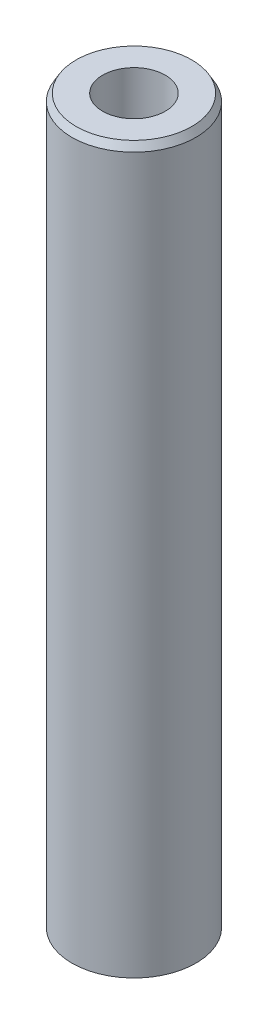
SolidWorks part; units mm, degrees
ref_plane "Front Plane" through (0, 0, 0) normal (0, 0, 1) x (1, 0, 0)
ref_plane "Top Plane" through (0, 0, 0) normal (0, 1, 0) x (1, 0, 0)
ref_plane "Right Plane" through (0, 0, 0) normal (1, 0, 0) x (0, 0, -1)
sketch "Sketch1" plane through (0, 0, 0) normal (0, 1, 0) x (1, 0, 0)
  circle A0 centre (0, 0) radius 25
  dimension "SHAFT_OD" = 50
extrude "Boss-Extrude1" add sketch "Sketch1" along normal blind 292.9998
sketch "Sketch2" plane through (0, 0, 0) normal (0, 1, 0) x (1, 0, 0)
  circle A0 centre (0, 0) radius 12.6338
  dimension "BORE_D" = 25.2675
extrude "Cut-Extrude1" cut sketch "Sketch2" along normal through all
chamfer "Chamfer1" distance 2.9389 angle 30 2 edges at (0, 292.9998, 25) (0, 0, 25) first distance on face at (0, 292.9998, 25) first distance on face at (0, 0, 12.6338)
